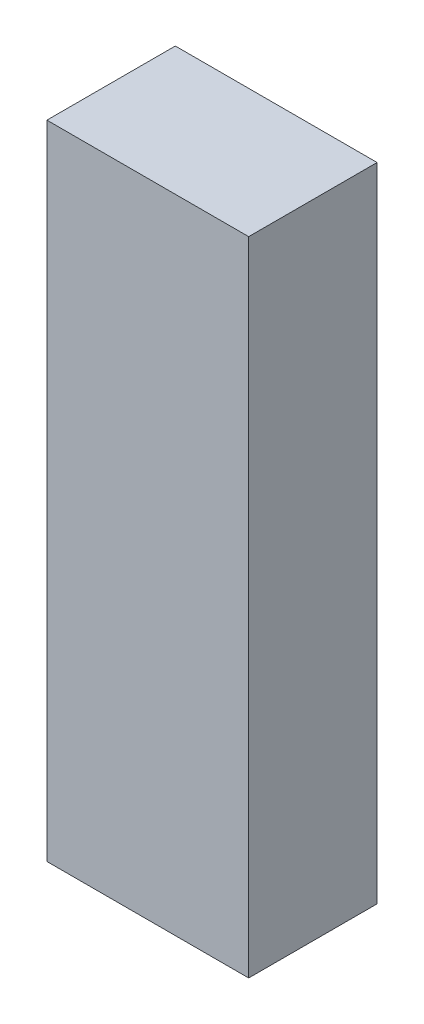
SolidWorks part; units mm, degrees
ref_plane "Front Plane" through (0, 0, 0) normal (0, 0, 1) x (1, 0, 0)
ref_plane "Top Plane" through (0, 0, 0) normal (0, 1, 0) x (1, 0, 0)
ref_plane "Right Plane" through (0, 0, 0) normal (1, 0, 0) x (0, 0, -1)
sketch "Sketch1" plane through (0, 0, 0) normal (0, 0, 1) x (1, 0, 0)
  line L1 (0, 0) -> (33, 0)
  line L2 (0, 0) -> (0, 105)
  line L3 (0, 105) -> (33, 105)
  line L4 (33, 0) -> (33, 105)
  dimension "D1" = 105
  dimension "D2" = 33
extrude "Boss-Extrude1" add sketch "Sketch1" along normal blind 21
